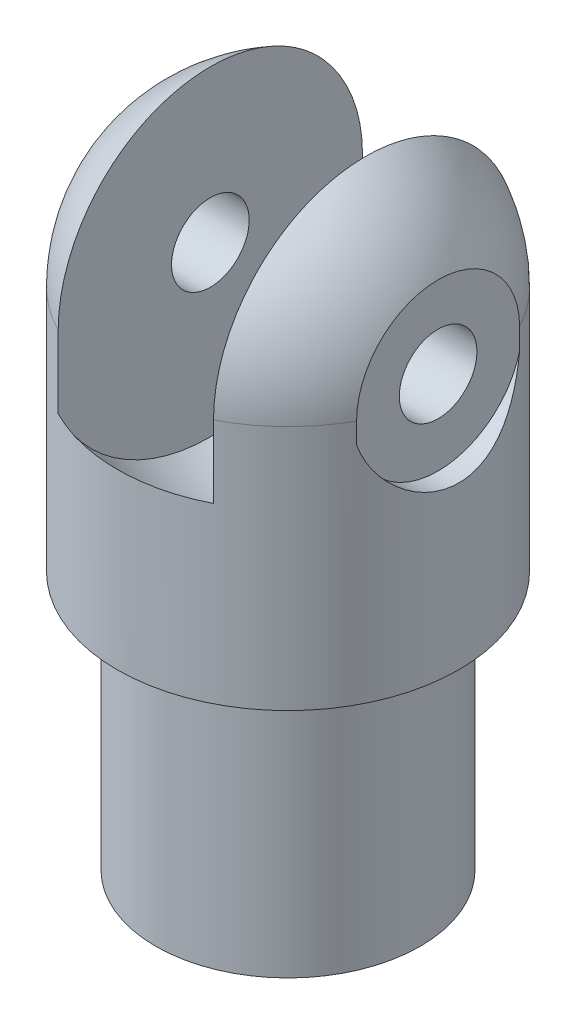
SolidWorks part; units mm, degrees
ref_plane "Front Plane" through (0, 0, 0) normal (0, 0, 1) x (1, 0, 0)
ref_plane "Top Plane" through (0, 0, 0) normal (0, 1, 0) x (1, 0, 0)
ref_plane "Right Plane" through (0, 0, 0) normal (1, 0, 0) x (0, 0, -1)
sketch "Sketch1" plane through (0, 0, 0) normal (0, 1, 0) x (1, 0, 0)
  circle A0 centre (0, 0) radius 12.9794
  dimension "D1" = 25.9588
extrude "Boss-Extrude1" add sketch "Sketch1" along normal blind 25.4 contours A0
sketch "Sketch2" plane through (0, 0, 0) normal (1, 0, 0) x (0, 0, -1)
  line L0 (-16.764, 25.4) -> (-16.764, 49.53)
  line L1 (0, 25.4) -> (-16.764, 25.4)
  line L4 (12.9794, 25.4) -> (-12.9794, 25.4) construction
  line L5 (0, 18.4404) -> (0, -18.4404) construction
  line L6 (0, 25.4) -> (0, 66.294)
  arc A0 (0, 66.294) -> (-16.764, 49.53) centre (0, 49.53) ccw
  dimension "D1" = 33.528
  dimension "D2" = 24.13
revolve "Revolve1" add sketch "Sketch2" angle 360 about L6
sketch "Sketch3" plane through (0, 0, 0) normal (1, 0, 0) x (0, 0, -1)
  line L2 (16.764, 49.53) -> (-16.764, 49.53) construction
  circle A2 centre (0, 49.53) radius 3.81
extrude "Cut-Extrude1" cut sketch "Sketch3" against normal through all both and the other way through all
sketch "Sketch4" plane through (0, 0, 0) normal (0, 0, 1) x (1, 0, 0)
  line L0 (16.3253, 49.53) -> (-16.3253, 49.53) construction
  line L1 (-7.62, 32.9954) -> (-7.62, 49.53)
  line L2 (-7.62, 49.53) -> (7.62, 49.53)
  line L3 (7.62, 49.53) -> (7.62, 32.9954)
  arc A0 (-7.62, 32.9954) -> (7.62, 32.9954) centre (0, 49.53) ccw
  dimension "D1" = 15.24
revolve "Cut-Revolve1" cut sketch "Sketch4" angle 360 about L2
ref_plane "Plane1" through (16.764, 0, 0) normal (1, 0, 0) x (0, 0, -1)
sketch "Sketch6" plane through (16.764, 0, 0) normal (1, 0, 0) x (0, 0, -1)
  circle A0 centre (0, 49.53) radius 8.255
extrude "Cut-Extrude2" cut sketch "Sketch6" against normal blind 2.032
mirror "Mirror1" about plane through (0, 0, 0) normal (1, 0, 0) of "Cut-Extrude2"
